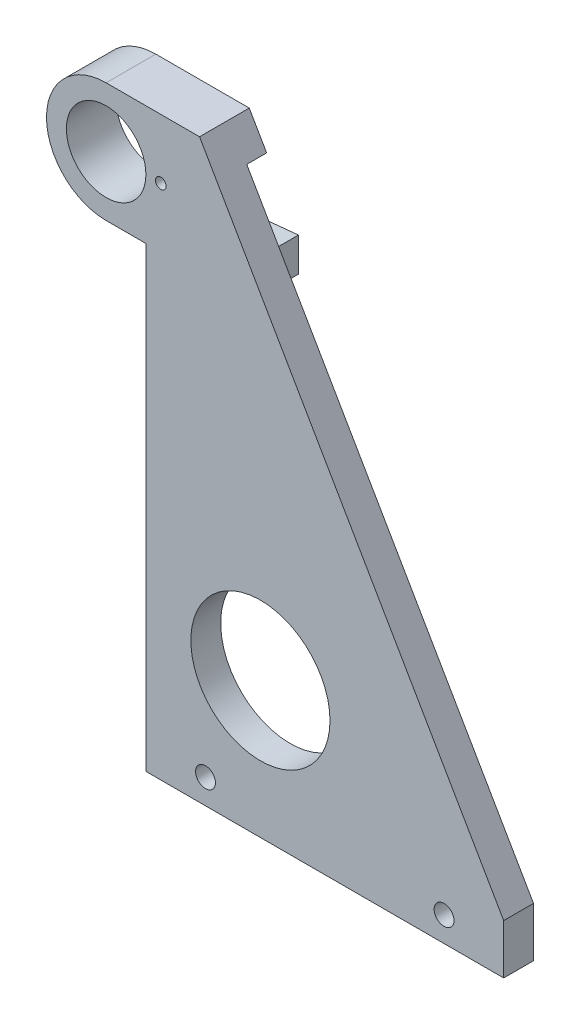
SolidWorks part; units mm, degrees
ref_plane "前视基准面" through (0, 0, 0) normal (0, 0, 1) x (1, 0, 0)
ref_plane "上视基准面" through (0, 0, 0) normal (0, 1, 0) x (1, 0, 0)
ref_plane "右视基准面" through (0, 0, 0) normal (1, 0, 0) x (0, 0, -1)
sketch "草图1" plane through (0, 0, 0) normal (0, 0, 1) x (1, 0, 0)
  line L0 (-18, 0) -> (18, 0)
  line L1 (18, 0) -> (18, 5)
  line L2 (18, 5) -> (-12.5996, 58)
  line L3 (-12.5996, 58) -> (-28, 58)
  line L4 (-28, 58) -> (-28, 46)
  line L5 (-28, 46) -> (-18, 46)
  line L6 (-18, 46) -> (-18, 0)
  point P3 (-28, 52)
  point P4 (0, 0)
  dimension "D1" = 36
  dimension "D2" = 5
  dimension "D3" = 12
  dimension "D4" = 47
  dimension "D5" = 120
  dimension "D6" = 10
extrude "凸台-拉伸1" add sketch "草图1" along normal blind 3
sketch "草图3" plane through (0, 0, 3) normal (0, 0, 1) x (1, 0, 0)
  circle A0 centre (-6.4764, 13.6875) radius 7
  dimension "D1" = 14
extrude "切除-拉伸1" cut sketch "草图3" against normal through all
sketch "草图4" plane through (0, 0, 3) normal (0, 0, 1) x (1, 0, 0)
  line L0 (-18, 5) -> (18, 0) construction
  line L1 (-18, 0) -> (18, 0) construction
  line L2 (-18, 0) -> (-18, 5) construction
  line L3 (-18, 5) -> (18, 5) construction
  line L4 (18, 0) -> (18, 5) construction
  line L5 (18, 5) -> (-18, 0) construction
  line L6 (-1000, 2.5) -> (49000, 2.5) construction
  line L7 (0, -997.5) -> (0, 49002.5) construction
  circle A0 centre (12, 2.5) radius 1
  circle A1 centre (-12, 2.5) radius 1
  point P9 (0, 2.5)
  dimension "D1" = 2
  dimension "D2" = 12
extrude "切除-拉伸2" cut sketch "草图4" against normal through all
fillet "圆角1" 2 edges at (-28, 58, 1.5) (-28, 46, 1.5) type full round first side face at (-20.2998, 58, 1.5) second side face at (-23, 46, 1.5) middle face at (-28, 52, 1.5)
sketch "草图6" plane through (0, 0, 0) normal (0, 0, -1) x (-1, 0, 0)
  line L0 (22, 58) -> (12.5996, 58)
  line L1 (12.5996, 58) -> (7.6508, 49.4285)
  line L2 (-18, 5) -> (12.5996, 58) construction
  line L3 (7.6508, 49.4285) -> (7.6508, 46)
  line L4 (7.6508, 46) -> (22, 46)
  arc A0 (22, 46) -> (22, 58) centre (22, 52) ccw
  point P2 (8.9597, 46)
  point P12 (6.8583, 46)
  point P13 (0, 0)
  point P14 (0, 0)
  point P15 (7.6508, 46)
extrude "凸台-拉伸2" add sketch "草图6" along normal blind 2
sketch "草图7" plane through (0, 0, 3) normal (0, 0, 1) x (1, 0, 0)
  circle A0 centre (-22, 52) radius 4
  dimension "D1" = 8
extrude "切除-拉伸3" cut sketch "草图7" against normal through all
sketch "草图8" plane through (0, 0, -2) normal (0, 0, -1) x (-1, 0, 0)
  line L0 (21.1705, 55.913) -> (21.1705, 48.087)
  line L1 (21.1705, 48.087) -> (7.0213, 49.4729)
  line L2 (7.0213, 49.4729) -> (7.0213, 54.6187)
  line L3 (7.0213, 54.6187) -> (21.1705, 55.913)
  line L4 (22, 58) -> (12.5996, 58) construction
  line L5 (7.6508, 46) -> (22, 46) construction
  circle A0 centre (22, 52) radius 4 construction
  arc A1 (22, 46) -> (22, 58) centre (22, 52) ccw construction
  dimension "D1" = 5.227
  dimension "D2" = 0.8295
  dimension "D3" = 5.595
  dimension "D4" = 14.1491
extrude "切除-拉伸4" cut sketch "草图8" against normal up to surface (2 mm away) up to face at (-2.5503, 24.4048, 0)
sketch "草图9" plane through (0, 0, 0) normal (0, 0, -1) x (-1, 0, 0)
  circle A0 centre (16.5, 52) radius 0.5371
  circle A2 centre (23, 52) radius 4.3196 construction
  arc A3 (22, 46) -> (22, 58) centre (22, 52) ccw construction
  dimension "D1" = 6.5
  dimension "D2" = 1
  dimension "D3" = 1.0743
extrude "切除-拉伸5" cut sketch "草图9" against normal through all
sketch "草图10" plane through (0, 0, 0) normal (0, 0, -1) x (-1, 0, 0)
  circle A0 centre (12, 2.5) radius 1.85
  circle A1 centre (-12, 2.5) radius 1.85
  dimension "D1" = 3.7
extrude "切除-拉伸6" cut sketch "草图10" against normal blind 1.5
